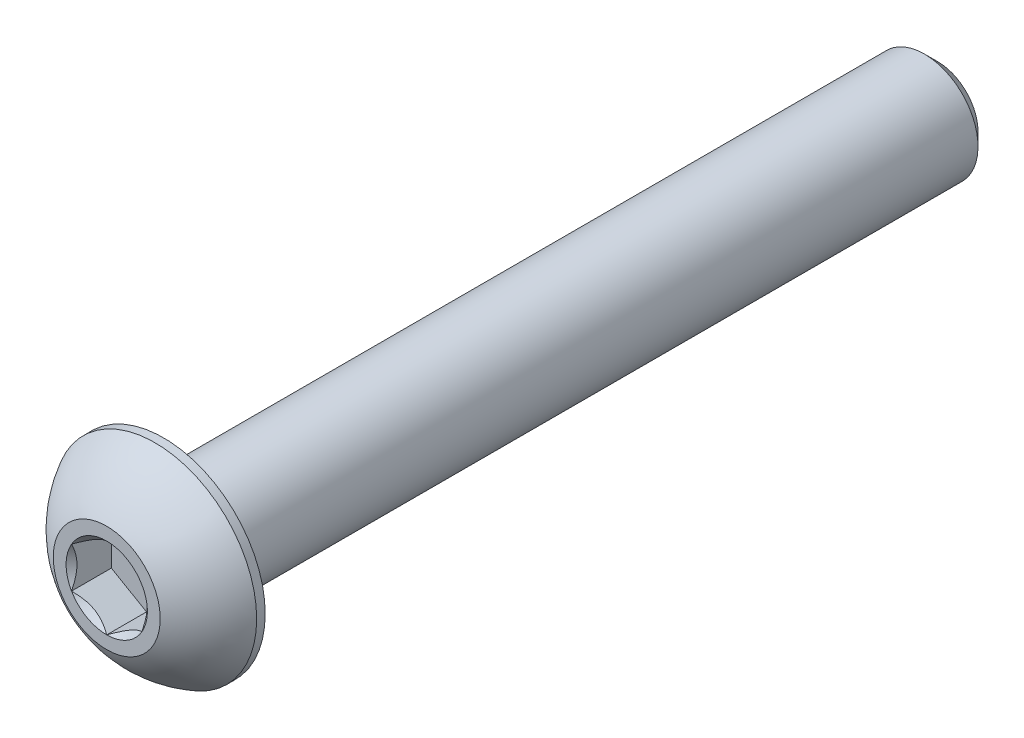
SolidWorks part; units mm, degrees
material "Plain Carbon Steel"
ref_plane "Front" through (0, 0, 0) normal (0, 0, 1) x (1, 0, 0)
ref_plane "Top" through (0, 0, 0) normal (0, 1, 0) x (1, 0, 0)
ref_plane "Right" through (0, 0, 0) normal (1, 0, 0) x (0, 0, -1)
sketch "Sketch1" plane through (0, 0, 0) normal (1, 0, 0) x (0, 0, -1)
  line L2 (2.5654, 2.413) -> (37.4904, 2.413)
  line L3 (37.4904, 2.413) -> (37.4904, 0)
  line L4 (37.4904, 0) -> (2.5654, 0)
  line L6 (2.1806, 4.5847) -> (2.5654, 4.5847) construction
  line L7 (37.4904, 2.413) -> (37.4904, -2.413) construction
  line L8 (0, 0) -> (2.5654, 0) construction
  line L9 (2.5654, 4.5847) -> (2.5654, -4.5847) construction
  line L11 (2.5654, 2.413) -> (2.5654, 0)
  line L13 (0, 1.5875) -> (0, -1.5875) construction
  line L14 (0, 1.5875) -> (0, 2.413) construction
  arc A3 (0, 2.413) -> (2.1806, 4.5847) centre (4.5749, 0) cw construction
  dimension "D1" = 0.3848
revolve "Revolve1" add sketch "Sketch1" angle 360 mid plane about L4
sketch "Sketch3" plane through (0, 0, -37.4904) normal (0, 0, -1) x (-1, 0, 0)
  circle A0 centre (0, 0) radius 2.413
curve "Helix/Spiral1" pitch 0.7937 height 35.7188 turns 45
sketch "Sketch2" plane through (0, 0, 0) normal (1, 0, 0) x (0, 0, -1)
  line L0 (37.4904, 2.413) -> (38.1849, 2.413)
  line L1 (38.1849, 2.413) -> (37.8873, 1.8974)
  line L2 (37.8873, 1.8974) -> (37.7881, 1.8974)
  line L3 (37.7881, 1.8974) -> (37.4904, 2.413)
  line L4 (37.6392, 2.1552) -> (38.0361, 2.1552) construction
  dimension "D1" = 60
  dimension "D2" = 0.0992
  dimension "D3" = 0.3969
chamfer "Chamfer1" distance 0.5953 angle 45 1 edges at (0, 2.413, -37.4904)
sweep "Cut-Sweep1" [suppressed] cut profiles "Sketch2" path "Helix/Spiral1"
sketch "Sketch7" plane through (0, 0, 0) normal (1, 0, 0) x (0, 0, -1)
  line L6 (2.1806, 4.5847) -> (2.5654, 4.5847) construction
  line L8 (0, 0) -> (2.5654, 0) construction
  line L11 (2.5654, 4.5847) -> (2.5654, -4.5847) construction
  line L12 (2.1806, 4.5847) -> (2.5654, 4.5847)
  line L13 (0, 0) -> (2.5654, 0)
  line L14 (0, 1.5875) -> (0, -1.5875) construction
  line L15 (2.5654, 4.5847) -> (2.5654, 0)
  line L16 (0, 2.413) -> (0, 0)
  arc A2 (2.1806, 4.5847) -> (0, 2.413) centre (4.5749, 0) ccw construction
  arc A3 (2.1806, 4.5847) -> (0, 2.413) centre (4.5749, 0) ccw
revolve "Revolve2" add sketch "Sketch7" angle 360 mid plane about L13
sketch "Sketch5" plane through (0, 0, 0) normal (0, 0, 1) x (1, 0, 0)
  line L1 (1.5875, -0.9165) -> (1.5875, 0.9165)
  line L2 (1.5875, 0.9165) -> (0, 1.8331)
  line L3 (0, 1.8331) -> (-1.5875, 0.9165)
  line L4 (-1.5875, 0.9165) -> (-1.5875, -0.9165)
  line L5 (-1.5875, -0.9165) -> (0, -1.8331)
  line L6 (0, -1.8331) -> (1.5875, -0.9165)
  circle A0 centre (0, 0) radius 1.5875 construction
extrude "Cut-Extrude2" cut sketch "Sketch5" against normal blind 1.7958
sketch "Sketch6" plane through (0, 0, 0) normal (0, 0, 1) x (1, 0, 0)
  circle A0 centre (0, 0) radius 1.8331
extrude "Cut-Extrude3" cut sketch "Sketch6" against normal blind 1.7958 draft 45
sketch "Sketch9" [suppressed] plane through (0, 0, -2.5654) normal (0, 0, 1) x (1, 0, 0)
  circle A2 centre (0, 0) radius 2.413
extrude "Boss-Extrude2" [suppressed] add sketch "Sketch9" against normal offset from surface (9.525 mm away) 31.75
sketch "Sketch10" plane through (0, 0, 0) normal (1, 0, 0) x (0, 0, -1)
  line L0 (37.4904, 2.413) -> (37.4904, -2.413) construction
  point P0 (36.2998, -2.413)
  dimension "D1" = 1.1906
equation "\"D3@Helix/Spiral1\" = \"Lg@Sketch1\" + \"D4@Helix/Spiral1\""
equation "\"D2@Sketch2\" = \"D4@Helix/Spiral1\" * .125"
equation "\"D3@Sketch2\" = \"D4@Helix/Spiral1\" * .5"
equation "\"D1@Chamfer1\" = \"D4@Helix/Spiral1\" * .75"
equation "\"D1@Cut-Extrude2\" = \"Head Ht@Sketch1\" * .7"
equation "\"D1@Sketch1\" = \"Head Ht@Sketch1\" * .15"
equation "\"D1@Sketch10\" = \"D4@Helix/Spiral1\" * 1.5"
equation "\"D1@Cut-Extrude3\" = \"D1@Cut-Extrude2\""
